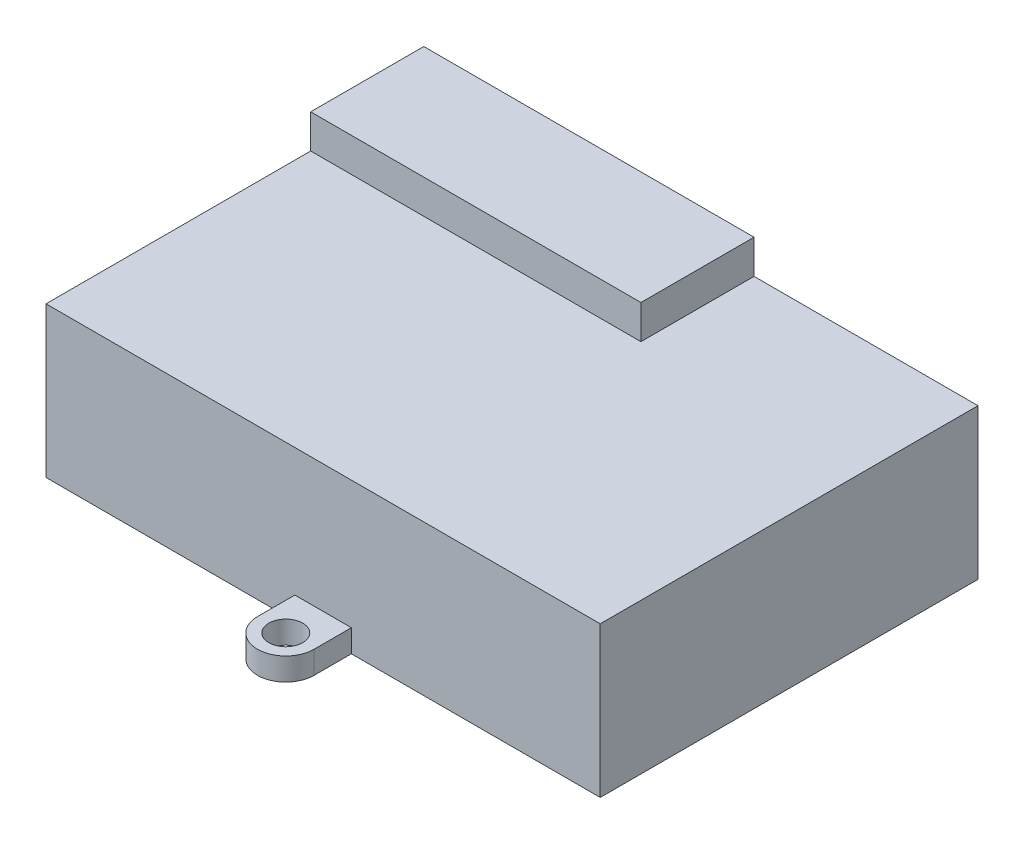
SolidWorks part; units mm, degrees
ref_plane "Front Plane" through (0, 0, 0) normal (0, 0, 1) x (1, 0, 0)
ref_plane "Top Plane" through (0, 0, 0) normal (0, 1, 0) x (1, 0, 0)
ref_plane "Right Plane" through (0, 0, 0) normal (1, 0, 0) x (0, 0, -1)
sketch "Sketch1" plane through (0, 0, 0) normal (0, 1, 0) x (1, 0, 0)
  line L0 (0, 20) -> (0, -20) construction
  line L1 (-24.5, 16.7) -> (-2.5, 16.7)
  line L2 (-24.5, 16.7) -> (-24.5, -16.7)
  line L3 (-24.5, -16.7) -> (-2.5, -16.7)
  line L4 (24.5, 16.7) -> (24.5, -16.7)
  line L5 (-24.5, 16.7) -> (24.5, -16.7) construction
  line L6 (-24.5, -16.7) -> (24.5, 16.7) construction
  line L7 (-2.5, -20) -> (-2.5, -16.7)
  line L8 (2.5, -20) -> (2.5, -16.7)
  line L9 (2.5, -16.7) -> (24.5, -16.7)
  line L10 (-2.5, 20) -> (-2.5, 16.7)
  line L11 (2.5, 20) -> (2.5, 16.7)
  line L12 (2.5, 16.7) -> (24.5, 16.7)
  line L13 (-2.5, 16.7) -> (2.5, 16.7)
  line L14 (-2.5, -16.7) -> (2.5, -16.7)
  circle A0 centre (0, 20) radius 1.5
  circle A1 centre (0, -20) radius 1.5
  arc A2 (-2.5, -20) -> (2.5, -20) centre (0, -20) ccw
  arc A3 (2.5, 20) -> (-2.5, 20) centre (0, 20) ccw
  circle A4 centre (0, -20) radius 2.5 construction
  circle A5 centre (0, 20) radius 2.5 construction
  point P0 (0, 0)
  point P9 (0, 0)
  dimension "D4" = 3
  dimension "D5" = 3
  dimension "D1" = 49
  dimension "D2" = 33.4
  dimension "D3" = 40
  dimension "D6" = 1
extrude "Boss-Extrude1" add sketch "Sketch1" along normal blind 13.3 contours L3 L14 L9 L4 L12 L13 L1 L2 region at (0, 0, 0)
extrude "Boss-Extrude2" add sketch "Sketch1<3>" along normal blind 2 contours L7 A2 L8 L14 A1 | L11 A3 L10 L13 A0 region at (-2.4234, 0, -18.35) region at (0, 0, 16.7766)
sketch "Sketch1<3>" plane through (0, 0, 0) normal (0, 1, 0) x (1, 0, 0) same geometry as "Sketch1"
sketch "Sketch2" plane through (0, 0, 0) normal (0, 1, 0) x (1, 0, 0)
  line L1 (-24.5, 16.7) -> (4.7, 16.7)
  line L2 (-24.5, 16.7) -> (-24.5, 6.7)
  line L3 (-24.5, 6.7) -> (4.7, 6.7)
  line L4 (4.7, 16.7) -> (4.7, 6.7)
  dimension "D1" = 29.2
  dimension "D2" = 10
extrude "Boss-Extrude3" add sketch "Sketch2" along normal blind 16.3
